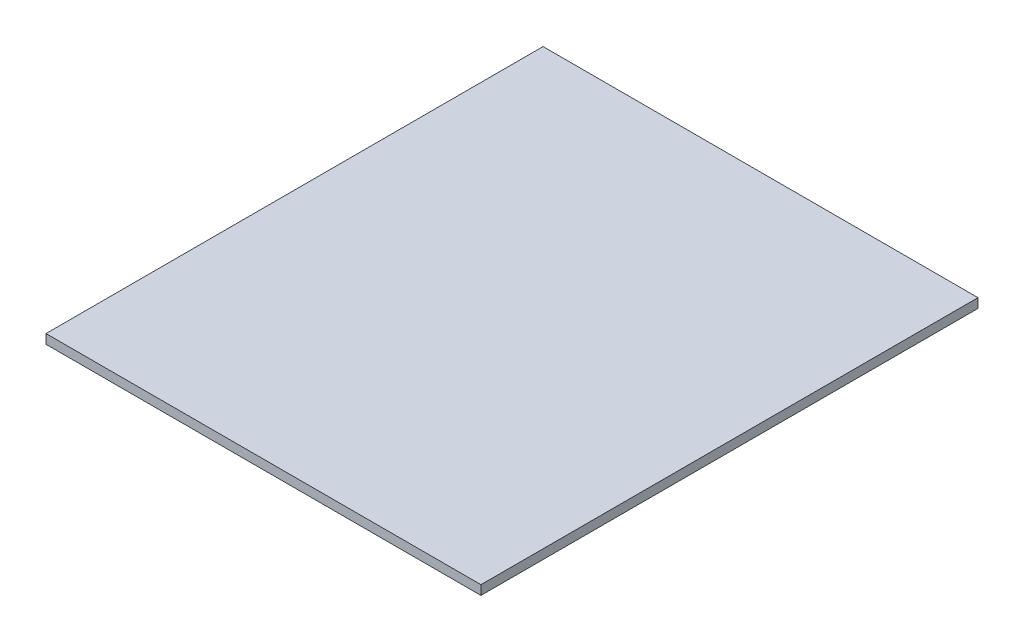
SolidWorks part; units mm, degrees
material "Cedar"
ref_plane "Front" through (0, 0, 0) normal (0, 0, 1) x (1, 0, 0)
ref_plane "Top" through (0, 0, 0) normal (0, 1, 0) x (1, 0, 0)
ref_plane "Right" through (0, 0, 0) normal (1, 0, 0) x (0, 0, -1)
sketch "Sketch1" plane through (0, 0, 0) normal (0, 1, 0) x (1, 0, 0)
  line L1 (-266.7, -304.8) -> (266.7, -304.8)
  line L2 (-266.7, -304.8) -> (-266.7, 304.8)
  line L3 (-266.7, 304.8) -> (266.7, 304.8)
  line L4 (266.7, -304.8) -> (266.7, 304.8)
  line L5 (-266.7, -304.8) -> (266.7, 304.8) construction
  line L6 (-266.7, 304.8) -> (266.7, -304.8) construction
  point P0 (0, 0)
  dimension "D1" = 609.6
  dimension "D2" = 533.4
extrude "Boss-Extrude1" add sketch "Sketch1" along normal blind 11.4554 contours L1 L4 L3 L2
